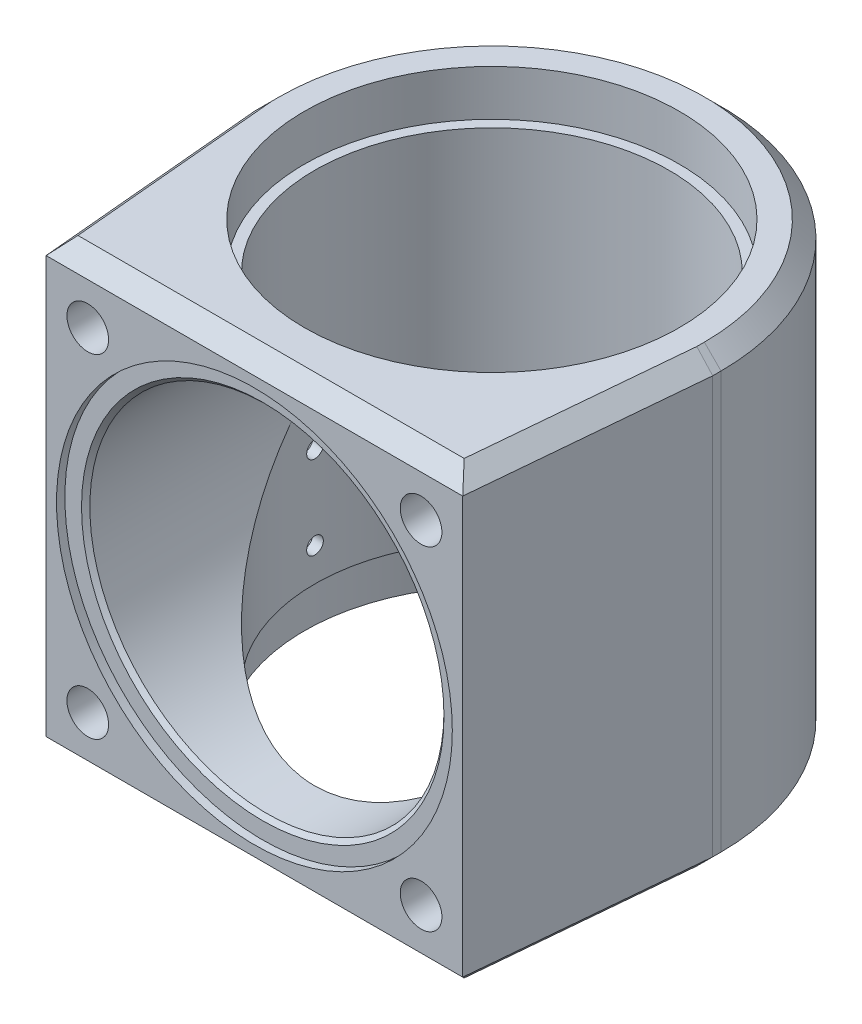
SolidWorks part; units mm, degrees
ref_plane "前视基准面" through (0, 0, 0) normal (0, 0, 1) x (1, 0, 0)
ref_plane "上视基准面" through (0, 0, 0) normal (0, 1, 0) x (1, 0, 0)
ref_plane "右视基准面" through (0, 0, 0) normal (1, 0, 0) x (0, 0, -1)
other "Configuration Table"
sketch "草图1" plane through (0, 0, 0) normal (0, 1, 0) x (1, 0, 0)
  line L0 (-55, 0) -> (55, 0)
  line L1 (55, 0) -> (55, 57)
  line L2 (0, 112) -> (0, 0) construction
  line L3 (-55, 0) -> (-55, 57)
  arc A0 (55, 57) -> (-55, 57) centre (0, 57) ccw
  point P5 (0, 111.3274)
  point P6 (0, 0)
  dimension "D1" = 110
  dimension "D2" = 57
extrude "凸台-拉伸1" add sketch "草图1" along normal blind 108
chamfer "倒角1" distance 55 distance2 5 1 edges at (-55, 54, 0) first distance on face at (-55, 54, -28.5)
chamfer "倒角2" distance 5 distance2 55 1 edges at (55, 54, 0) first distance on face at (2.5, 54, 0)
chamfer "倒角3" distance 4 angle 45 12 edges at (55, 0, -56) (0, 0, -112) (-55, 0, -56) (52.5, 0, -27.5) (-52.5, 0, -27.5) (0, 0, 0) (-55, 108, -56) (0, 108, -112) (55, 108, -56) (52.5, 108, -27.5) (-52.5, 108, -27.5) (0, 108, 0)
sketch "草图2" plane through (0, 108, 0) normal (0, 1, 0) x (1, 0, 0)
  circle A0 centre (0, 57) radius 42.5
  arc A1 (51, 57) -> (-51, 57) centre (0, 57) ccw construction
  point P2 (0, 0)
  dimension "D1" = 85
extrude "切除-拉伸1" cut sketch "草图2" against normal blind 108
sketch "草图3" plane through (0, 108, 0) normal (0, 1, 0) x (1, 0, 0)
  circle A0 centre (0, 57) radius 45
  dimension "D1" = 90
extrude "切除-拉伸2" cut sketch "草图3" against normal blind 11
extrude "切除-拉伸3" cut sketch "草图3<2>" along normal blind 11 from offset 108 offset against normal yes
sketch "草图3<2>" plane through (0, 108, 0) normal (0, 1, 0) x (1, 0, 0) same geometry as "草图3"
sketch "草图4" plane through (0, 0, 0) normal (0, 0, 1) x (1, 0, 0)
  line L0 (0, 0) -> (0, 108) construction
  line L1 (-46.3471, 108) -> (46.3471, 108) construction
  line L2 (-55, 54) -> (50, 54) construction
  line L3 (-55, 4) -> (-55, 104) construction
  line L4 (50, 4) -> (50, 104) construction
  circle A0 centre (40, 94) radius 5
  circle A1 centre (40, 14) radius 5
  circle A2 centre (-40, 14) radius 5
  circle A3 centre (-40, 94) radius 5
  dimension "D1" = 10
  dimension "D2" = 80
  dimension "D3" = 80
extrude "切除-拉伸4" cut sketch "草图4" against normal blind 21
ref_plane "基准面2" through (0, 19, 0) normal (0, -1, 0) x (-1, 0, 0)
ref_plane "基准面3" through (0, 39, 0) normal (0, -1, 0) x (-1, 0, 0)
sketch "草图6" plane through (0, 19, 0) normal (0, -1, 0) x (-1, 0, 0)
  line L0 (55, 57) -> (30.0385, 57) construction
  line L1 (55, 57) -> (55, 52)
  line L2 (55, 52) -> (45, 52)
  line L3 (45, 52) -> (45, 55)
  line L4 (45, 55) -> (35, 55)
  line L5 (35, 55) -> (35, 57)
  line L6 (55, 57) -> (35, 57)
  dimension "D1" = 5
  dimension "D2" = 10
  dimension "D3" = 2
  dimension "D4" = 10
revolve "切除-旋转1" cut sketch "草图6" angle 360 about L0
sketch "草图7" plane through (0, 39, 0) normal (0, -1, 0) x (-1, 0, 0)
  line L0 (55, 57) -> (30.0385, 57) construction
  line L1 (35, 55) -> (35, 57) construction
  line L2 (45, 52) -> (45, 55) construction
  line L3 (45, 55) -> (35, 55) construction
  line L4 (55, 57) -> (35, 57) construction
  line L5 (55, 57) -> (55, 52) construction
  line L6 (55, 52) -> (45, 52) construction
  line L7 (55, 57) -> (30.0385, 57) construction
  line L8 (35, 55) -> (35, 57)
  line L9 (45, 52) -> (45, 55)
  line L10 (45, 55) -> (35, 55)
  line L11 (55, 57) -> (35, 57)
  line L12 (55, 57) -> (55, 52)
  line L13 (55, 52) -> (45, 52)
revolve "切除-旋转2" cut sketch "草图7" angle 360 about L7
sketch "草图8" plane through (0, 0, 0) normal (0, 0, 1) x (1, 0, 0)
  line L0 (0, 0) -> (0, 108) construction
  circle A0 centre (0, 54) radius 47.5
  dimension "D1" = 95
extrude "切除-拉伸5" cut sketch "草图8" against normal blind 2
sketch "草图9" plane through (0, 0, -2) normal (0, 0, 1) x (1, 0, 0)
  circle A2 centre (0, 54) radius 42.5
  circle A3 centre (0, 54) radius 42.5
  dimension "D1" = 5
extrude "切除-拉伸6" cut sketch "草图9" against normal up to next
chamfer "倒角4" distance 1 angle 45 1 edges at (42.5, 54, -2)
